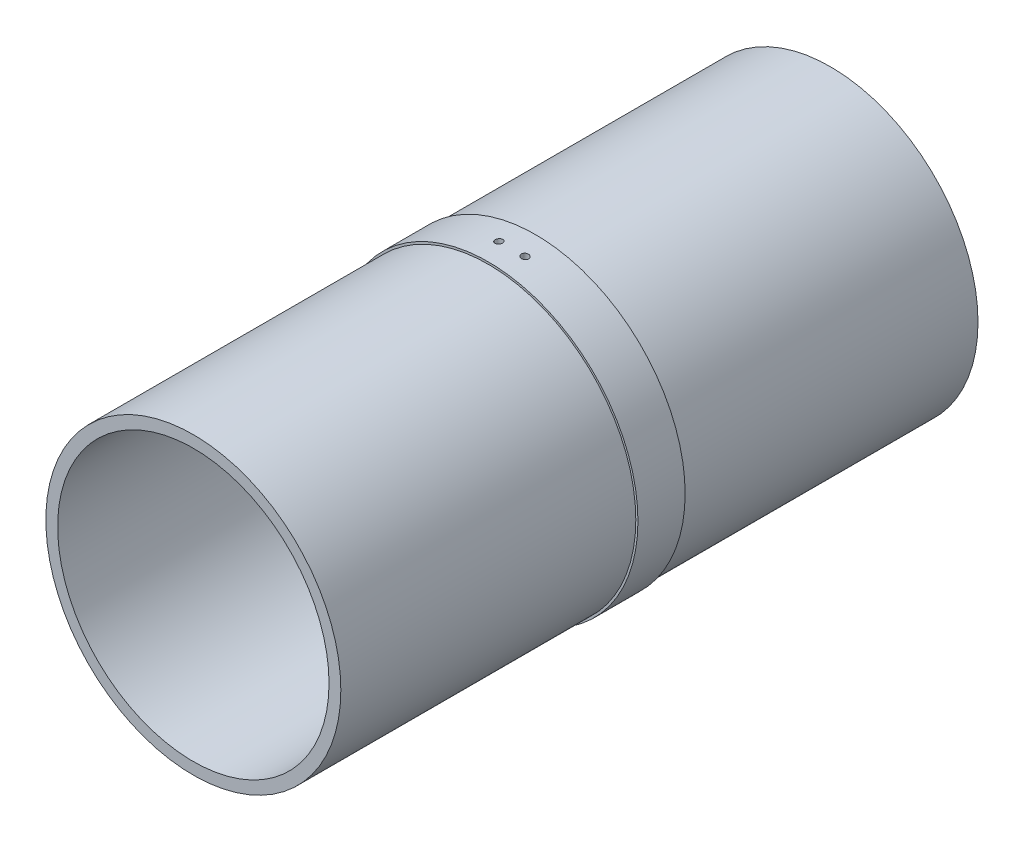
SolidWorks part; units mm, degrees
ref_plane "Front Plane" through (0, 0, 0) normal (0, 0, 1) x (1, 0, 0)
ref_plane "Top Plane" through (0, 0, 0) normal (0, 1, 0) x (1, 0, 0)
ref_plane "Right Plane" through (0, 0, 0) normal (1, 0, 0) x (0, 0, -1)
sketch "Sketch1" plane through (0, 0, 0) normal (0, 0, 1) x (1, 0, 0)
  circle A0 centre (0, 0) radius 79.375
  circle A1 centre (0, 0) radius 73.025
  dimension "D1" = 158.75
  dimension "D2" = 6.35
extrude "Boss-Extrude1" add sketch "Sketch1" along normal blind 342.9
ref_plane "Plane1" through (0, 0, 171.45) normal (0, 0, 1) x (1, 0, 0)
sketch "Sketch2" plane through (0, 0, 171.45) normal (0, 0, 1) x (1, 0, 0)
  circle A0 centre (0, 0) radius 79.375 construction
  circle A1 centre (0, 0) radius 79.375
  circle A2 centre (0, 0) radius 80.518
extrude "Boss-Extrude2" add sketch "Sketch2" against normal mid plane 25.4
sketch "Sketch5" plane through (0, 0, 171.45) normal (0, 0, 1) x (1, 0, 0)
  line L0 (0, 0) -> (0, 47.1719) construction
  line L1 (0, 0) -> (7.0176, 80.2116) construction
  circle A1 centre (0, 0) radius 80.518 construction
  point P2 (0, 0)
  point P5 (8.3839, 95.8285)
  point P7 (0, 0)
  point P8 (0, 0)
  dimension "D1" = 5
ref_plane "Plane2" through (7.0176, 80.2116, 0) normal (0.0872, 0.9962, 0) x (0, 0, 1)
hole_wizard "5/32 (0.15625) Diameter Hole1" positions "Sketch9" profile "Sketch10" hole size "5/32" standard "ANSI Inch" end condition up to next
sketch "Sketch9" plane through (7.0176, 80.2116, 0) normal (0.0872, 0.9962, 0) x (0, 0, 1)
  point P0 (171.45, 0)
sketch "Sketch10" plane through (7.0176, 80.2116, 171.45) normal (0, 0, 1) x (-0.9962, 0.0872, 0)
  line L0 (0, 0) -> (0, 7.493)
  line L1 (0, 7.493) -> (1.9844, 7.493)
  line L2 (1.9844, 7.493) -> (1.9844, 0)
  line L5 (1.9844, 0) -> (0, 0)
  line L11 (0, -6.35) -> (0, 107.95) construction
  dimension "Thru Hole Dia." = 3.9688
  dimension "Thru Hole Depth" = 7.493
mirror "Mirror1" about plane through (0, 0, 0) normal (1, 0, 0) of "5/32 (0.15625) Diameter Hole1"
